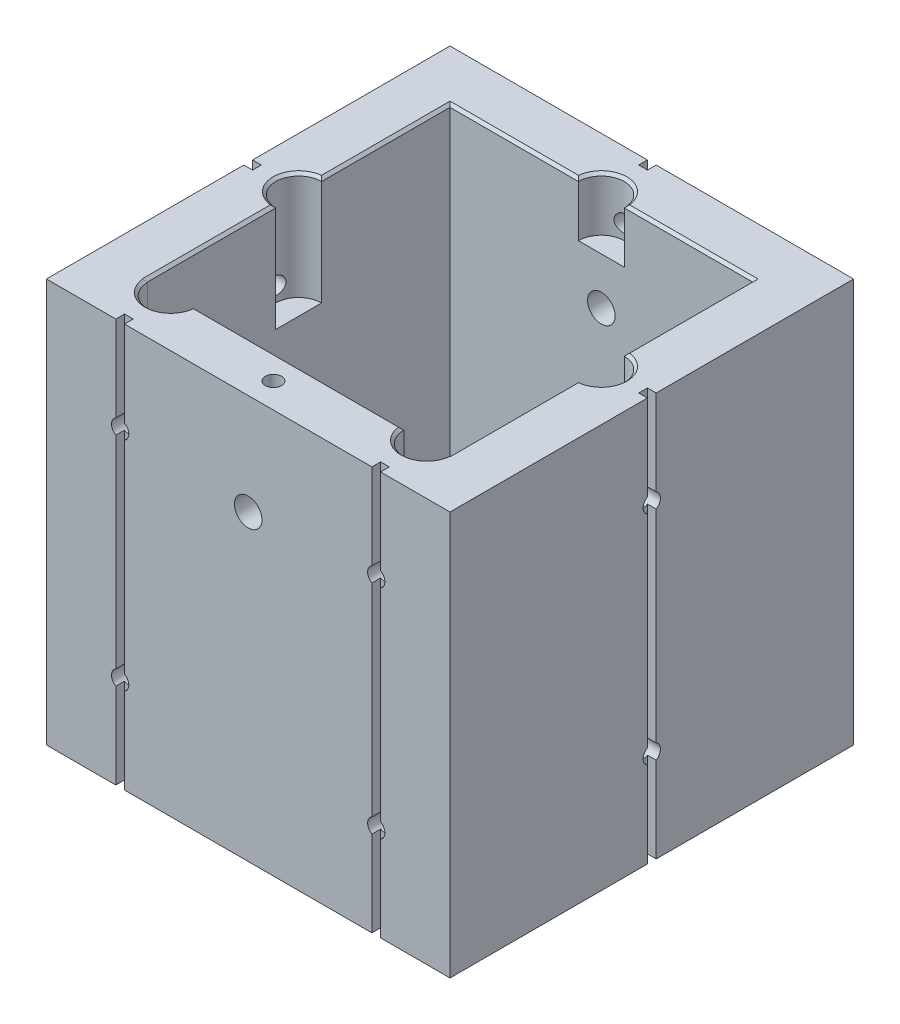
SolidWorks part; units mm, degrees
ref_plane "Front Plane" through (0, 0, 0) normal (0, 0, 1) x (1, 0, 0)
ref_plane "Top Plane" through (0, 0, 0) normal (0, 1, 0) x (1, 0, 0)
ref_plane "Right Plane" through (0, 0, 0) normal (1, 0, 0) x (0, 0, -1)
sketch "Sketch1" plane through (0, 0, 0) normal (0, 1, 0) x (1, 0, 0)
  line L1 (74.8, 74.8) -> (0, 74.8)
  line L2 (74.8, 74.8) -> (74.8, 0)
  line L3 (74.8, 0) -> (0, 0)
  line L4 (0, 74.8) -> (0, 0)
  line L5 (74.8, 74.8) -> (0, 0) construction
  line L6 (74.8, 0) -> (0, 74.8) construction
  line L7 (65.45, 65.45) -> (9.35, 65.45)
  line L8 (65.45, 65.45) -> (65.45, 9.35)
  line L9 (65.45, 9.35) -> (9.35, 9.35)
  line L10 (9.35, 65.45) -> (9.35, 9.35)
  line L11 (65.45, 65.45) -> (9.35, 9.35) construction
  line L12 (65.45, 9.35) -> (9.35, 65.45) construction
  point P0 (37.4, 37.4)
  point P6 (37.4, 37.4)
  dimension "D1" = 74.8
  dimension "D2" = 74.8
  dimension "D3" = 56.1
  dimension "D4" = 56.1
extrude "Boss-Extrude1" add sketch "Sketch1" along normal blind 74.8
sketch "Sketch2" plane through (0, 0, -74.8) normal (0, 0, -1) x (-1, 0, 0)
  line L0 (-74.8, 74.8) -> (0, 74.8) construction
  line L3 (0, 74.8) -> (0, 0) construction
  circle A0 centre (-37.4, 56.1) radius 2.555
  dimension "D1" = 5.11
  dimension "D3" = 37.4
  dimension "D2" = 18.7
extrude "Cut-Extrude1" cut sketch "Sketch2" against normal blind 74.8
sketch "Sketch3" plane through (0, 74.8, 0) normal (0, 1, 0) x (1, 0, 0)
  line L0 (38.21, 74.8) -> (38.21, 73.18)
  line L1 (74.8, 74.8) -> (0, 74.8)
  line L2 (74.8, 74.8) -> (74.8, 0)
  line L3 (74.8, 0) -> (0, 0)
  line L4 (0, 74.8) -> (0, 0)
  line L5 (74.8, 74.8) -> (0, 0) construction
  line L6 (74.8, 0) -> (0, 74.8) construction
  line L7 (38.21, 73.18) -> (36.59, 73.18)
  line L8 (36.59, 73.18) -> (36.59, 74.8)
  point P0 (37.4, 37.4)
  point P6 (37.4, 73.18)
  line M14 (74.8, 74.8) -> (0, 74.8)
  dimension "D1" = 1.62
  dimension "D2" = 1.62
  dimension "D3" = 37.4
extrude "Cut-Extrude2" cut sketch "Sketch3" against normal blind 74.8 contours L8 L7 L0 M14 region at (37.4, 74.8, -73.99)
ref_axis "Axis1" through (74.8, 74.8, -74.8) along (-0.7071, 0, 0.7071)
ref_plane "Plane1" through (0, 0, 0) normal (0.7071, 0, 0.7071) x (-0.7071, 0, 0.7071)
mirror "Mirror1" about plane through (0, 0, 0) normal (0.7071, 0, 0.7071) of "Cut-Extrude2"
ref_axis "Axis2" through (0, 74.8, -74.8) along (0.7071, 0, 0.7071)
ref_plane "Plane2" through (37.4, 0, -37.4) normal (0.7071, 0, -0.7071) x (0.7071, 0, 0.7071)
mirror "Mirror2" about plane through (37.4, 0, -37.4) normal (0.7071, 0, -0.7071) of "Cut-Extrude2"
chamfer "Chamfer1" distance 0.5 angle 45 4 edges at (37.4, 74.8, -65.45) (65.45, 74.8, -37.4) (37.4, 74.8, -9.35) (9.35, 74.8, -37.4)
sketch "Sketch4" plane through (0, 74.8, 0) normal (0, 1, 0) x (1, 0, 0)
  line L0 (60.325, 0) -> (60.325, 1.62)
  line L1 (0, 0) -> (74.8, 0) construction
  line L2 (60.325, 1.62) -> (61.945, 1.62)
  line L3 (61.945, 1.62) -> (61.945, 0)
  line L4 (37.4, 0) -> (37.4, 8.85) construction
  line L5 (65.95, 8.85) -> (8.85, 8.85) construction
  line L6 (12.855, 1.62) -> (12.855, 0)
  line L7 (14.475, 1.62) -> (12.855, 1.62)
  line L8 (14.475, 0) -> (14.475, 1.62)
  line L10 (74.8, 74.8) -> (0, 74.8)
  line L11 (74.8, 74.8) -> (74.8, 0)
  line L12 (74.8, 0) -> (0, 0)
  line L13 (0, 74.8) -> (0, 0)
  line L14 (74.8, 74.8) -> (0, 0) construction
  line L15 (74.8, 0) -> (0, 74.8) construction
  point P7 (47.47, 0)
  point P8 (37.4, 0)
  point P10 (61.135, 1.62)
  point P18 (37.4, 37.4)
  line M18 (0, 0) -> (74.8, 0)
  dimension "D1" = 10.07
  dimension "D2" = 13.665
  dimension "D3" = 1.62
  dimension "D4" = 1.62
extrude "Cut-Extrude3" cut sketch "Sketch4" against normal blind 74.8 contours L8 L7 L6 M18 | L3 L2 L0 M18 region at (61.135, 74.8, -0.81) region at (13.665, 74.8, -0.81)
sketch "Sketch5" plane through (0, 74.8, 0) normal (0, 1, 0) x (1, 0, 0)
  line L0 (65.45, 65.45) -> (9.35, 65.45) construction
  line L1 (0, 0) -> (74.8, 0)
  line L2 (0, 0) -> (0, 74.8)
  line L3 (0, 74.8) -> (74.8, 74.8)
  line L4 (74.8, 0) -> (74.8, 74.8)
  line L5 (34.65, 68.45) -> (40.15, 68.45)
  line L6 (40.15, 68.45) -> (40.15, 65.45)
  line L7 (34.65, 68.45) -> (34.65, 65.45)
  line L8 (38.21, 73.18) -> (36.59, 73.18) construction
  line L9 (33.15, 65.45) -> (41.65, 65.45)
  arc A0 (41.65, 65.45) -> (33.15, 65.45) centre (37.4, 65.45) ccw
  point P7 (37.4, 68.45)
  point P16 (37.4, 73.18)
  line M11 (8.85, 65.95) -> (65.95, 65.95)
  dimension "D1" = 3
  dimension "D3" = 8.5
  dimension "D2" = 5.5
extrude "Cut-Extrude4" cut sketch "Sketch5" against normal blind 10 contours A0 L9 L7 M11 | A0 L7 L5 L6 M11 | L9 A0 L6 M11 | L7 L9 L6 M11 | L5 L7 L6 M11 region at (34.5576, 74.8, -67.2) region at (37.4, 74.8, -67.2) region at (37.4, 74.8, -65.7) region at (33.9049, 74.8, -65.6992) region at (40.8951, 74.8, -65.6992)
sketch "Sketch6" plane through (0, 74.8, 0) normal (0, 1, 0) x (1, 0, 0)
  line L0 (9.35, 65.45) -> (9.35, 9.35) construction
  line L1 (0, 0) -> (74.8, 0)
  line L2 (0, 0) -> (0, 74.8)
  line L3 (0, 74.8) -> (74.8, 74.8)
  line L4 (74.8, 0) -> (74.8, 74.8)
  line L5 (65.45, 9.35) -> (65.45, 65.45) construction
  line L6 (9.35, 9.35) -> (65.45, 9.35) construction
  line L7 (14.475, 1.62) -> (12.855, 1.62) construction
  line L8 (60.325, 1.62) -> (61.945, 1.62) construction
  line L10 (65.385, 9.35) -> (65.45, 9.35)
  line L11 (17.915, 9.35) -> (56.885, 9.35)
  line L12 (9.415, 9.35) -> (9.415, 65.45)
  line L13 (9.415, 65.45) -> (65.45, 65.45)
  line L14 (65.45, 9.35) -> (65.45, 33.15)
  line L15 (65.45, 41.65) -> (65.45, 65.45)
  line L16 (9.35, 41.65) -> (9.35, 33.15)
  line L17 (9.415, 9.35) -> (17.915, 9.35)
  line L18 (56.885, 9.35) -> (65.45, 9.35)
  line L19 (65.45, 33.15) -> (65.45, 41.65)
  arc A0 (9.35, 41.65) -> (9.35, 33.15) centre (9.35, 37.4) ccw
  arc A1 (65.45, 33.15) -> (65.45, 41.65) centre (65.45, 37.4) ccw
  arc A2 (56.885, 9.35) -> (65.385, 9.35) centre (61.135, 9.35) ccw
  arc A3 (9.415, 9.35) -> (17.915, 9.35) centre (13.665, 9.35) ccw
  point P23 (13.665, 1.62)
  point P26 (61.135, 1.62)
  line M19 (65.95, 65.95) -> (65.95, 8.85)
  line M20 (65.95, 8.85) -> (8.85, 8.85)
  line M21 (8.85, 8.85) -> (8.85, 65.95)
  dimension "D1" = 8.5
extrude "Cut-Extrude5" cut sketch "Sketch6" against normal blind 20 contours L16 A0 M21 | A0 M21 | A3 L17 M20 | A3 M20 | A2 M20 | A2 L18 M20 | A1 M19 | L19 A1 M19 region at (61.135, 74.8, -9.1003) region at (7.2732, 74.8, -37.4) region at (9.1003, 74.8, -37.4) region at (61.135, 74.8, -7.2732) region at (65.6997, 74.8, -37.4) region at (13.665, 74.8, -9.1003) region at (67.5268, 74.8, -37.4) region at (13.665, 74.8, -7.2732)
sketch "Sketch7" plane through (0, 0, 0) normal (0, -1, 0) x (-1, 0, 0)
  line L0 (-9.35, 9.35) -> (-65.45, 9.35) construction
  line L1 (0, 74.8) -> (-74.8, 74.8)
  line L2 (0, 74.8) -> (0, 0)
  line L3 (0, 0) -> (-74.8, 0)
  line L4 (-74.8, 74.8) -> (-74.8, 0)
  line L5 (-9.35, 65.45) -> (-9.35, 9.35) construction
  line L6 (-65.45, 65.45) -> (-9.35, 65.45) construction
  line L7 (-65.45, 9.35) -> (-65.45, 65.45) construction
  line L8 (-60.325, 1.62) -> (-61.945, 1.62) construction
  line L9 (-14.475, 1.62) -> (-12.855, 1.62) construction
  line L10 (-9.35, 33.15) -> (-9.35, 41.65)
  line L12 (-33.15, 65.45) -> (-41.65, 65.45)
  line L14 (-65.45, 41.65) -> (-65.45, 33.15)
  line L15 (-65.45, 33.15) -> (-65.45, 9.35)
  line L16 (-65.45, 9.35) -> (-56.885, 9.35)
  line L17 (-56.885, 9.35) -> (-17.915, 9.35)
  line L18 (-17.915, 9.35) -> (-9.35, 9.35)
  line L19 (-9.35, 9.35) -> (-9.35, 33.15)
  line L21 (-9.35, 65.45) -> (-65.45, 65.45)
  line L22 (-9.35, 65.45) -> (-9.35, 9.35)
  line L23 (-9.35, 9.35) -> (-65.45, 9.35)
  line L24 (-65.45, 65.45) -> (-65.45, 9.35)
  circle A0 centre (-61.135, 9.35) radius 4.25
  circle A1 centre (-13.665, 9.35) radius 4.25
  circle A2 centre (-9.35, 37.4) radius 4.25
  circle A3 centre (-37.4, 65.45) radius 4.25
  circle A4 centre (-65.45, 37.4) radius 4.25
  point P27 (-61.135, 1.62)
  point P30 (-13.665, 1.62)
  line M33 (-65.45, 65.45) -> (-9.35, 65.45)
  line M34 (-9.35, 65.45) -> (-9.35, 9.35)
  line M35 (-9.35, 9.35) -> (-65.45, 9.35)
  line M36 (-65.45, 9.35) -> (-65.45, 65.45)
  dimension "D1" = 8.5
extrude "Cut-Extrude6" cut sketch "Sketch7" against normal blind 20 contours L23 A1 | A0 M35 | A4 M36 | A3 M33 | A2 M34 region at (7.5462, 0, -37.4) region at (13.665, 0, -7.5462) region at (37.4, 0, -67.2538) region at (61.135, 0, -7.5462) region at (67.2538, 0, -37.4)
chamfer "Chamfer2" distance 0.5 angle 45 5 edges at (37.4, 74.8, -69.7) (5.1, 74.8, -37.4) (13.665, 74.8, -5.1) (69.7, 74.8, -37.4) (61.135, 74.8, -5.1)
sketch "Sketch8" plane through (74.8, 0, 0) normal (1, 0, 0) x (0, 0, -1)
  line L1 (0, 37.4) -> (74.8, 37.4) construction
  line L2 (36.59, 0) -> (36.59, 74.8) construction
  line L3 (0, 74.8) -> (0, 0) construction
  line L5 (74.8, 74.8) -> (74.8, 0) construction
  line L7 (38.21, 0) -> (36.59, 0) construction
  circle A0 centre (37.4, 17.25) radius 1.6
  circle A1 centre (37.4, 57.55) radius 1.6
  dimension "D2" = 3.2
  dimension "D1" = 0.81
  dimension "D3" = 17.25
extrude "Cut-Extrude7" cut sketch "Sketch8" against normal blind 80
sketch "Sketch9" plane through (0, 0, 0) normal (0, 0, 1) x (1, 0, 0)
  line L0 (0, 37.4) -> (74.8, 37.4) construction
  line L2 (0, 74.8) -> (0, 0) construction
  line L4 (74.8, 74.8) -> (74.8, 0) construction
  line L5 (61.945, 0) -> (61.945, 74.8) construction
  line L6 (60.325, 0) -> (61.945, 0) construction
  line L7 (37.4, 74.8) -> (37.4, 0) construction
  line L8 (14.475, 74.8) -> (60.325, 74.8) construction
  line L9 (14.475, 0) -> (60.325, 0) construction
  circle A0 centre (61.135, 17.25) radius 1.6
  circle A1 centre (13.665, 17.25) radius 1.6
  circle A2 centre (61.135, 57.55) radius 1.6
  circle A3 centre (13.665, 57.55) radius 1.6
  point P15 (61.135, 0)
  dimension "D3" = 3.2
  dimension "D1" = 0.81
  dimension "D2" = 17.25
extrude "Cut-Extrude8" cut sketch "Sketch9" against normal blind 10
sketch "Sketch11" plane through (0, 0, -73.18) normal (0, 0, -1) x (-1, 0, 0)
  line L0 (-36.59, 0) -> (-36.59, 53.6768) construction
  line L2 (-36.59, 0) -> (0, 0) construction
  line L6 (-74.8, 74.8) -> (-38.21, 74.8) construction
  circle A0 centre (-37.4, 17.25) radius 1.6
  circle A1 centre (-37.4, 67.55) radius 1.6
  dimension "D1" = 3.2
  dimension "D2" = 0.81
  dimension "D3" = 17.25
  dimension "D4" = 7.25
extrude "Cut-Extrude9" cut sketch "Sketch11" against normal blind 10
sketch "Sketch12" plane through (0, 74.8, 0) normal (0, 1, 0) x (1, 0, 0)
  line L0 (74.8, 0) -> (0, 0)
  line L1 (17.915, 9.35) -> (17.915, 0)
  line L3 (0, 0) -> (74.8, 0)
  line L4 (0, 0) -> (0, 74.8)
  line L5 (0, 74.8) -> (74.8, 74.8)
  line L6 (74.8, 0) -> (74.8, 74.8)
  circle A0 centre (37.4, 4.675) radius 1.5
  point P6 (37.4, 0)
  point P10 (17.915, 4.675)
  point P13 (72.0192, 70.7214)
  point P15 (30.7489, -0.9668)
  dimension "D1" = 3
extrude "Cut-Extrude10" cut sketch "Sketch12" against normal blind 20 contours A0 region at (37.4, 74.8, -4.675)
